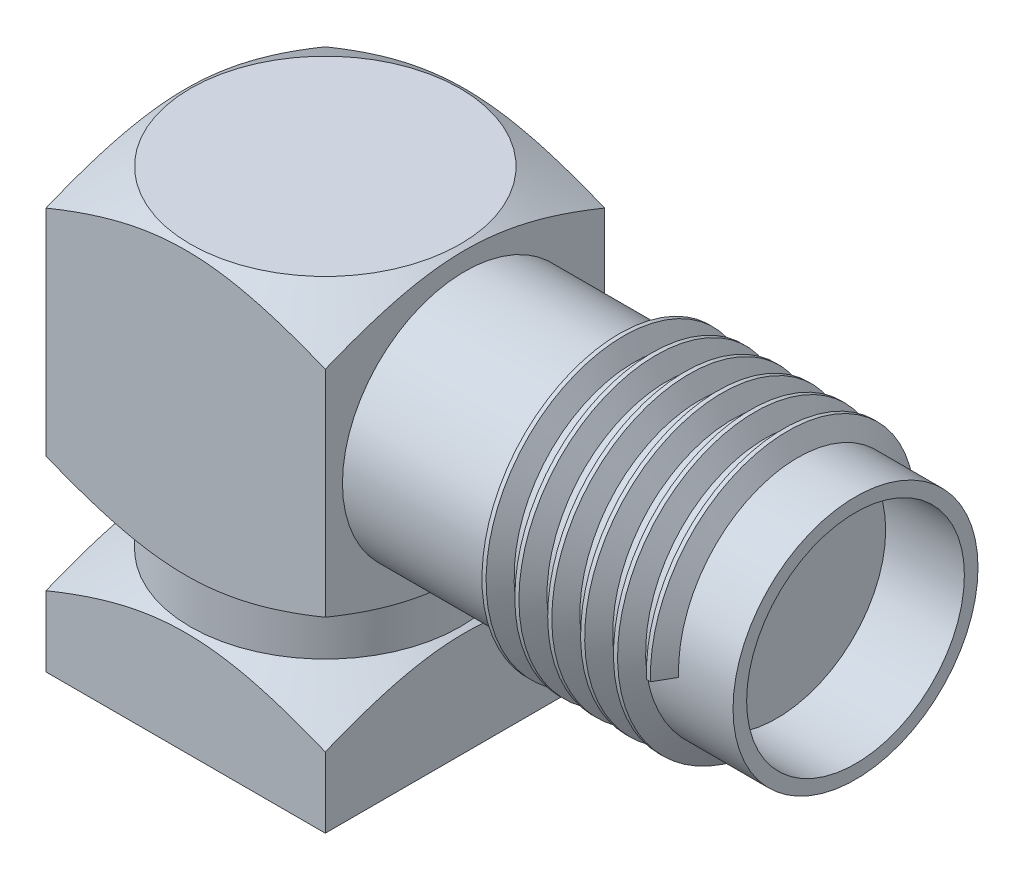
SolidWorks part; units mm, degrees
ref_plane "Front Plane" through (0, 0, 0) normal (0, 0, 1) x (1, 0, 0)
ref_plane "Top Plane" through (0, 0, 0) normal (0, 1, 0) x (1, 0, 0)
ref_plane "Right Plane" through (0, 0, 0) normal (1, 0, 0) x (0, 0, -1)
sketch "Sketch1" plane through (0, 0, 0) normal (0, 1, 0) x (1, 0, 0)
  line L1 (-2.9972, -2.9972) -> (2.9972, -2.9972)
  line L2 (-2.9972, -2.9972) -> (-2.9972, 2.9972)
  line L3 (-2.9972, 2.9972) -> (2.9972, 2.9972)
  line L4 (2.9972, -2.9972) -> (2.9972, 2.9972)
  line L5 (-2.9972, -2.9972) -> (2.9972, 2.9972) construction
  line L6 (-2.9972, 2.9972) -> (2.9972, -2.9972) construction
  point P0 (0, 0)
  dimension "D1" = 5.9944
  dimension "D2" = 5.9944
extrude "Boss-Extrude1" add sketch "Sketch1" along normal blind 9.398
sketch "Sketch2" plane through (0, 0, 0) normal (0, 0, 1) x (1, 0, 0)
  line L0 (-2.9972, 0) -> (2.9972, 0) construction
  line L1 (-2.8956, 3.2385) -> (2.8956, 3.2385)
  line L2 (-2.8956, 3.2385) -> (-2.8956, 2.286)
  line L3 (-2.8956, 2.286) -> (2.8956, 2.286)
  line L4 (2.8956, 3.2385) -> (2.8956, 2.286)
  line L5 (-2.8956, 3.2385) -> (2.8956, 2.286) construction
  line L6 (-2.8956, 2.286) -> (2.8956, 3.2385) construction
  line L7 (2.8956, 3.2385) -> (5.4609, 4.7196)
  line L8 (5.4609, 4.7196) -> (5.4609, 0.8049)
  line L9 (2.8956, 2.286) -> (5.4609, 0.8049)
  line L10 (0, 2.7623) -> (6.3357, 2.7623) construction
  line L11 (0, 2.7623) -> (0, 6.5009) construction
  line L16 (2.8956, 3.2385) -> (2.8956, 9.398)
  line L17 (-2.9972, 9.398) -> (2.9972, 9.398) construction
  line L18 (-2.9972, 9.398) -> (2.9972, 9.398)
  line L19 (2.8956, 9.398) -> (5.4609, 7.9169)
  line L20 (5.4609, 7.9169) -> (5.4609, 9.398)
  line L21 (5.4609, 9.398) -> (2.9972, 9.398)
  point P0 (0, 2.7622)
  point P14 (5.4609, 2.7623)
  dimension "D1" = 5.7912
  dimension "D2" = 0.9525
  dimension "D3" = 2.286
  dimension "D4" = 30
  dimension "D5" = 30
revolve "Cut-Revolve1" cut sketch "Sketch2" angle 360 about L11 region at (4.6058, 8.9043, 0) region at (4.4385, 2.7623, 0)
sketch "Sketch3" plane through (2.9972, 0, 0) normal (1, 0, 0) x (0, 0, -1)
  line L0 (-2.9972, 8.6226) -> (-2.9972, 4.0139) construction
  line L1 (-2.9972, 8.6226) -> (-2.9972, 4.0139)
  line L2 (-2.9972, 6.3183) -> (2.9972, 6.3183) construction
  line L3 (2.9972, 8.6226) -> (2.9972, 4.0139) construction
  circle A0 centre (0, 6.3183) radius 2.6289
extrude "Boss-Extrude2" add sketch "Sketch3" along normal blind 8.382 contours A0 L2 | L2 A0 region at (2.9972, 7.434, 0) region at (2.9972, 5.2025, 0)
thread "Thread1" pitch 0.7056 method extrude profile "Thread Profile1" start angle 0, offset 1.1684, length 3.81, pitch 0.7056, diameter 5.2578
ref_plane "Plane1" through (10.2108, 6.3183, 2.6289) normal (0, -1, 0) x (0, 0, 1)
sketch "Thread Profile1" plane through (10.2108, 6.3183, 2.6289) normal (0, -1, 0) x (0, 0, 1)
  line L0 (0, 0) -> (0, 0.7056) construction
  line L1 (0, 0) -> (0.3819, 0.2205)
  line L2 (0.3819, 0.2205) -> (0.3819, 0.3087)
  line L3 (0.3819, 0.3087) -> (0, 0.5292)
  line L4 (0.3819, 0.2646) -> (0, 0.2646) construction
  line L11 (0, 0) -> (0, 0.5292)
  point P2 (0, 0)
  dimension "Pitch" = 0.7056
  dimension "Profile_Angle" = 60
  dimension "Profile_Land" = 0.0882
  dimension "Profile_Height" = 0.3819
sketch "Sketch11" plane through (11.3792, 0, 0) normal (1, 0, 0) x (0, 0, -1)
  circle A1 centre (0, 6.3183) radius 2.3368
extrude "Cut-Extrude1" cut sketch "Sketch11" against normal blind 1.6891
